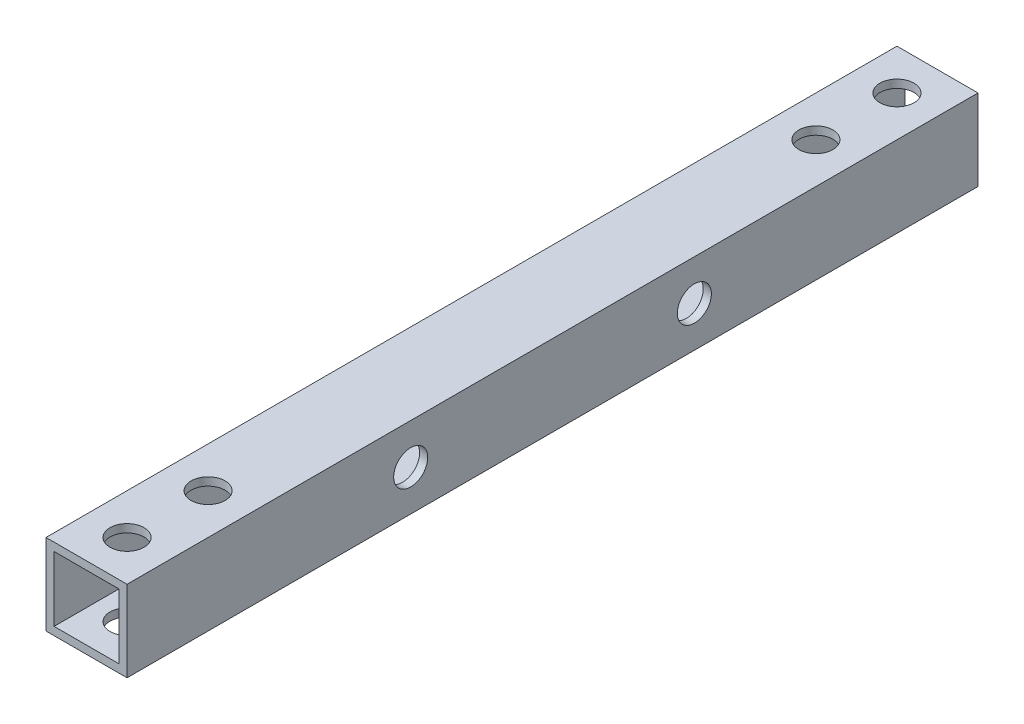
SolidWorks part; units mm, degrees
ref_plane "Front Plane" through (0, 0, 0) normal (0, 0, 1) x (1, 0, 0)
ref_plane "Top Plane" through (0, 0, 0) normal (0, 1, 0) x (1, 0, 0)
ref_plane "Right Plane" through (0, 0, 0) normal (1, 0, 0) x (0, 0, -1)
sketch "Sketch1" plane through (0, 0, 0) normal (0, 0, 1) x (1, 0, 0)
  line L0 (0, 0) -> (10, 0)
  line L1 (0, 0) -> (0, 10)
  line L2 (0, 10) -> (10, 10)
  line L3 (10, 0) -> (10, 10)
  line L4 (1, 9) -> (9, 9)
  line L5 (1, 9) -> (1, 1)
  line L6 (1, 1) -> (9, 1)
  line L7 (9, 9) -> (9, 1)
  dimension "D1" = 0
  dimension "D2" = 1
  dimension "D3" = 10
  dimension "D4" = 8
  dimension "D5" = 8
  dimension "D6" = 10
  dimension "D7" = 1
  dimension "D8" = 0
extrude "Boss-Extrude1" add sketch "Sketch1" along normal blind 105
sketch "Sketch2" plane through (0, 10, 0) normal (0, 1, 0) x (1, 0, 0)
  line L0 (10, 0) -> (0, 0) construction
  line L1 (10, -105) -> (10, 0) construction
  line L2 (10, -105) -> (0, -105) construction
  circle A0 centre (5, -5) radius 2.1
  circle A1 centre (5, -15) radius 2.1
  circle A2 centre (5, -100) radius 2.1
  circle A3 centre (5, -90) radius 2.1
  dimension "D1" = 4.2
  dimension "D2" = 4.2
  dimension "D3" = 5
  dimension "D5" = 5
  dimension "D6" = 5
  dimension "D7" = 4.2
  dimension "D8" = 4.2
  dimension "D9" = 5
  dimension "D10" = 5
  dimension "D11" = 5
  dimension "D12" = 15
  dimension "D4" = 15
extrude "Cut-Extrude1" cut sketch "Sketch2" against normal blind 116
sketch "Sketch4" plane through (10, 0, 0) normal (1, 0, 0) x (0, 0, -1)
  line L0 (0, 0) -> (0, 10) construction
  line L1 (-105, 0) -> (-105, 10) construction
  line L2 (-105, 10) -> (0, 10) construction
  circle A0 centre (-70, 5) radius 2.1
  circle A1 centre (-35, 5) radius 2.1
  dimension "D1" = 4.2
  dimension "D2" = 4.2
  dimension "D3" = 35
  dimension "D5" = 5
  dimension "D6" = 5
  dimension "D4" = 35
extrude "Cut-Extrude3" cut sketch "Sketch4" against normal blind 10
